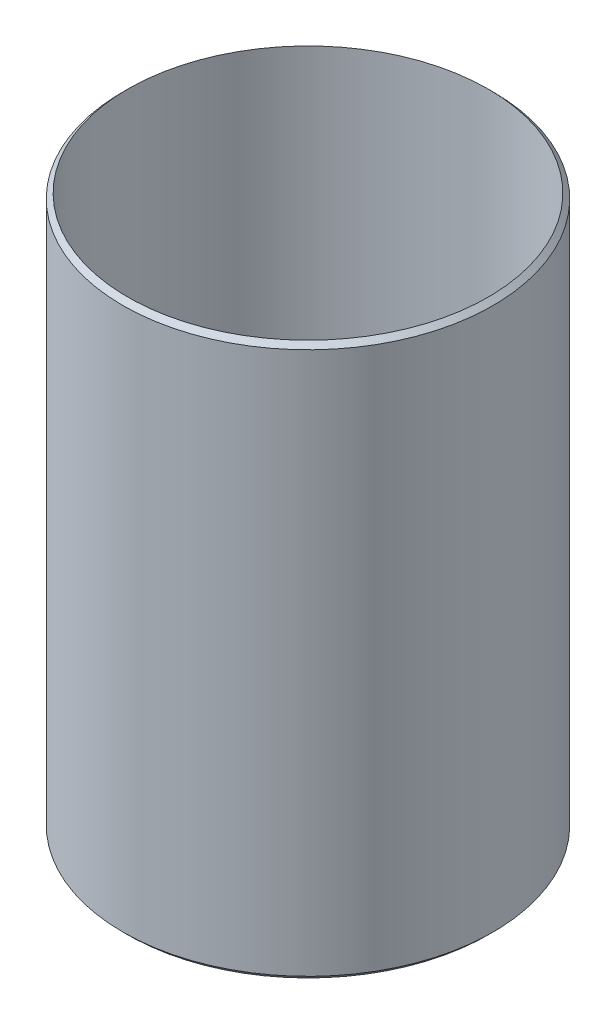
SolidWorks part; units mm, degrees
material "Plain Carbon Steel"
ref_plane "Front Plane" through (0, 0, 0) normal (0, 0, 1) x (1, 0, 0)
ref_plane "Top Plane" through (0, 0, 0) normal (0, 1, 0) x (1, 0, 0)
ref_plane "Right Plane" through (0, 0, 0) normal (1, 0, 0) x (0, 0, -1)
sketch "Sketch1" plane through (0, 0, 0) normal (0, 1, 0) x (1, 0, 0)
  circle A0 centre (0, 0) radius 74.2
  circle A1 centre (0, 0) radius 76.2
  dimension "D1" = 152.4
  dimension "D2" = 2
extrude "Boss-Extrude1" add sketch "Sketch1" along normal blind 227.4
chamfer "Chamfer1" distance 2 angle 45 2 edges at (0, 0, 76.2) (0, 227.4, 76.2)
equation "\"TubeDiameter\" = 6.000in"
equation "\"D1@Sketch1\"=\"TubeDiameter\""
